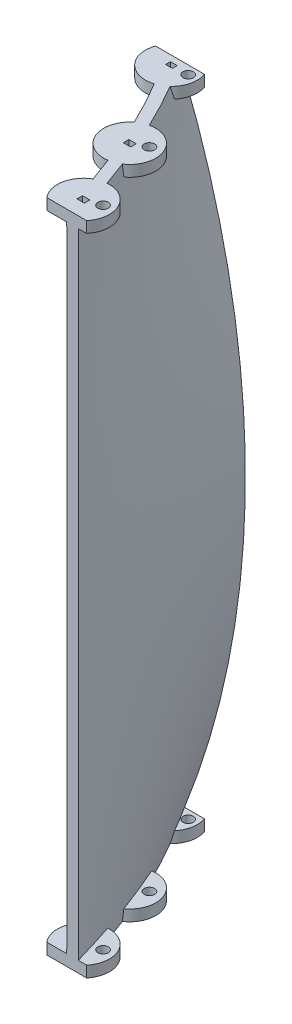
SolidWorks part; units mm, degrees
ref_plane "Plan de face" through (0, 0, 0) normal (0, 0, 1) x (1, 0, 0)
ref_plane "Plan de dessus" through (0, 0, 0) normal (0, 1, 0) x (1, 0, 0)
ref_plane "Plan de droite" through (0, 0, 0) normal (1, 0, 0) x (0, 0, -1)
ref_plane "Plan1" through (0, 0, 10) normal (0, 0, 1) x (1, 0, 0)
ref_plane "Plan2" through (0, 0, 60) normal (0, 0, 1) x (1, 0, 0)
sketch "Esquisse1" plane through (0, 0, 60) normal (0, 0, 1) x (1, 0, 0)
  line L1 (-235, -265) -> (235, -265)
  line L2 (-235, -265) -> (-235, 265)
  line L3 (-235, 265) -> (235, 265)
  line L4 (235, -265) -> (235, 265)
  line L5 (-235, -265) -> (235, 265) construction
  line L6 (-235, 265) -> (235, -265) construction
  point P0 (0, 0)
  dimension "D1" = 470
  dimension "D2" = 530
sketch "Esquisse2" plane through (0, 0, 10) normal (0, 0, 1) x (1, 0, 0)
  circle A0 centre (0, 0) radius 230
loft "Lissage1" add profiles "Esquisse2", "Esquisse1" connector at (-217.3645, 75.1842, 10) connector at (-235, 265, 60)
shell "Coque1" thickness 3 removed face at (0, 0, 60)
sketch "Esquisse3" plane through (0, 0, 13) normal (0, 0, 1) x (1, 0, 0)
  spline S4 degree 3 poles (-1744.7327, 376.1903) (-526.9338, -261.2431) (-3.804, -346.9049) (174.7035, -148.6101) (179.7346, -142.3812) (189.1199, -129.386) (193.4749, -122.6201) (198.4789, -113.8135) (199.4591, -112.0321) (201.3646, -108.4534) (202.2908, -106.6549) (204.9907, -101.232) (206.6856, -97.5804) (211.4617, -86.5187) (214.236, -79.0024) (218.9895, -63.6942) (220.9703, -55.9031) (222.9555, -45.9941) (223.3279, -44.0038) (224.0237, -40.0062) (224.3459, -38.0049) (225.2353, -32.0028) (225.7261, -28) (226.8998, -15.9875) (227.2865, -7.9737) (227.2836, 8.0646) (226.894, 16.0892) (225.9081, 26.1268) (225.6858, 28.1347) (225.1902, 32.1512) (224.9166, 34.1622) (224.021, 40.178) (223.3259, 44.156) (220.9479, 55.9928) (218.9722, 63.7545) (214.2305, 79.0156) (211.4628, 86.5145) (206.6954, 97.5584) (205.0032, 101.2055) (202.3067, 106.6237) (201.3815, 108.421) (199.4777, 111.9979) (198.4976, 113.78) (193.4909, 122.5945) (189.1338, 129.3656) (179.7439, 142.3695) (174.7107, 148.6017) (-4.1787, 347.3344) (-528.7451, 260.2995) (-1744.2878, -377.4815) knots -1.953743 -1.953743 -1.953743 -1.953743 0.0625 0.0625 0.125 0.125 0.1875 0.1875 0.203125 0.203125 0.21875 0.21875 0.25 0.25 0.3125 0.3125 0.375 0.375 0.390625 0.390625 0.40625 0.40625 0.4375 0.4375 0.5 0.5 0.5625 0.5625 0.578125 0.578125 0.59375 0.59375 0.625 0.625 0.6875 0.6875 0.75 0.75 0.78125 0.78125 0.796875 0.796875 0.8125 0.8125 0.875 0.875 0.9375 0.9375 2.957415 2.957415 2.957415 2.957415 only from (152.2162, -171.6485) to (152.2162, 171.6485)
  spline S5 degree 3 poles (-195.2618, -1771.3819) (316.1646, -491.0086) (344.6975, 32.7076) (130.3839, 188.7229) (124.6273, 192.5237) (112.7752, 199.5943) (106.68, 202.8645) (98.8449, 206.6138) (97.2671, 207.3467) (94.0897, 208.7785) (92.4898, 209.4774) (87.681, 211.5127) (84.4552, 212.7913) (74.7194, 216.3971) (68.1511, 218.4952) (54.8632, 222.0955) (48.1436, 223.5983) (34.5539, 226.0114) (27.684, 226.9224) (19.0006, 227.6836) (17.263, 227.8166) (13.7931, 228.0438) (12.0597, 228.1381) (6.8641, 228.3641) (3.4064, 228.4387) (-6.9486, 228.4367) (-13.828, 228.1355) (-27.5391, 226.9367) (-34.3709, 226.0386) (-44.5819, 224.2333) (-47.9794, 223.5547) (-53.0663, 222.4195) (-54.7604, 222.0216) (-58.1454, 221.1859) (-59.8336, 220.7489) (-68.2258, 218.4749) (-74.8099, 216.3655) (-87.7243, 211.5786) (-94.0544, 208.9004) (-106.4603, 202.9753) (-112.536, 199.7278) (-121.4549, 194.4207) (-124.3952, 192.5788) (-128.7561, 189.7046) (-130.2026, 188.7271) (-133.0695, 186.7413) (-134.4907, 185.7324) (-375.502, 10.4249) (-260.223, -622.6751) (244.4446, -1759.2058) knots -2.272579 -2.272579 -2.272579 -2.272579 0.0625 0.0625 0.125 0.125 0.1875 0.1875 0.203125 0.203125 0.21875 0.21875 0.25 0.25 0.3125 0.3125 0.375 0.375 0.4375 0.4375 0.453125 0.453125 0.46875 0.46875 0.5 0.5 0.5625 0.5625 0.625 0.625 0.65625 0.65625 0.671875 0.671875 0.6875 0.6875 0.75 0.75 0.8125 0.8125 0.875 0.875 0.90625 0.90625 0.921875 0.921875 0.9375 0.9375 3.594862 3.594862 3.594862 3.594862 only from (152.2162, 171.6485) to (-152.2162, 171.6485)
  spline S6 degree 3 poles (1744.7327, -376.1903) (526.9338, 261.2431) (3.804, 346.9049) (-174.7035, 148.6101) (-179.7346, 142.3812) (-189.1199, 129.386) (-193.4749, 122.6201) (-198.4789, 113.8135) (-199.4591, 112.0321) (-201.3646, 108.4534) (-202.2908, 106.6549) (-204.9907, 101.232) (-206.6856, 97.5804) (-211.4617, 86.5187) (-214.236, 79.0024) (-218.9895, 63.6942) (-220.9703, 55.9031) (-222.9555, 45.9941) (-223.3279, 44.0038) (-224.0237, 40.0062) (-224.3459, 38.0049) (-225.2353, 32.0028) (-225.7261, 28) (-226.8998, 15.9875) (-227.2865, 7.9737) (-227.2836, -8.0646) (-226.894, -16.0892) (-225.9081, -26.1268) (-225.6858, -28.1347) (-225.1902, -32.1512) (-224.9166, -34.1622) (-224.021, -40.178) (-223.3259, -44.156) (-220.9479, -55.9928) (-218.9722, -63.7545) (-214.2305, -79.0156) (-211.4628, -86.5145) (-206.6954, -97.5584) (-205.0032, -101.2055) (-202.3067, -106.6237) (-201.3815, -108.421) (-199.4777, -111.9979) (-198.4976, -113.78) (-193.4909, -122.5945) (-189.1338, -129.3656) (-179.7439, -142.3695) (-174.7107, -148.6017) (4.1787, -347.3344) (528.7451, -260.2995) (1744.2878, 377.4815) knots -1.953743 -1.953743 -1.953743 -1.953743 0.0625 0.0625 0.125 0.125 0.1875 0.1875 0.203125 0.203125 0.21875 0.21875 0.25 0.25 0.3125 0.3125 0.375 0.375 0.390625 0.390625 0.40625 0.40625 0.4375 0.4375 0.5 0.5 0.5625 0.5625 0.578125 0.578125 0.59375 0.59375 0.625 0.625 0.6875 0.6875 0.75 0.75 0.78125 0.78125 0.796875 0.796875 0.8125 0.8125 0.875 0.875 0.9375 0.9375 2.957415 2.957415 2.957415 2.957415 only from (-152.2162, 171.6485) to (-152.2162, -171.6485)
  spline S7 degree 3 poles (195.2618, 1771.3819) (-316.1646, 491.0086) (-344.6975, -32.7076) (-130.3839, -188.7229) (-124.6273, -192.5237) (-112.7752, -199.5943) (-106.68, -202.8645) (-98.8449, -206.6138) (-97.2671, -207.3467) (-94.0897, -208.7785) (-92.4898, -209.4774) (-87.681, -211.5127) (-84.4552, -212.7913) (-74.7194, -216.3971) (-68.1511, -218.4952) (-54.8632, -222.0955) (-48.1436, -223.5983) (-34.5539, -226.0114) (-27.684, -226.9224) (-19.0006, -227.6836) (-17.263, -227.8166) (-13.7931, -228.0438) (-12.0597, -228.1381) (-6.8641, -228.3641) (-3.4064, -228.4387) (6.9486, -228.4367) (13.828, -228.1355) (27.5391, -226.9367) (34.3709, -226.0386) (44.5819, -224.2333) (47.9794, -223.5547) (53.0663, -222.4195) (54.7604, -222.0216) (58.1454, -221.1859) (59.8336, -220.7489) (68.2258, -218.4749) (74.8099, -216.3655) (87.7243, -211.5786) (94.0544, -208.9004) (106.4603, -202.9753) (112.536, -199.7278) (121.4549, -194.4207) (124.3952, -192.5788) (128.7561, -189.7046) (130.2026, -188.7271) (133.0695, -186.7413) (134.4907, -185.7324) (375.502, -10.4249) (260.223, 622.6751) (-244.4446, 1759.2058) knots -2.272579 -2.272579 -2.272579 -2.272579 0.0625 0.0625 0.125 0.125 0.1875 0.1875 0.203125 0.203125 0.21875 0.21875 0.25 0.25 0.3125 0.3125 0.375 0.375 0.4375 0.4375 0.453125 0.453125 0.46875 0.46875 0.5 0.5 0.5625 0.5625 0.625 0.625 0.65625 0.65625 0.671875 0.671875 0.6875 0.6875 0.75 0.75 0.8125 0.8125 0.875 0.875 0.90625 0.90625 0.921875 0.921875 0.9375 0.9375 3.594862 3.594862 3.594862 3.594862 only from (-152.2162, -171.6485) to (152.2162, -171.6485)
  spline S8 degree 3 poles (152.2162, -171.6485) (158.2661, -166.2289) (163.9694, -160.534) (174.7035, -148.6101) (179.7346, -142.3812) (189.1199, -129.386) (193.4749, -122.6201) (198.4789, -113.8135) (199.4591, -112.0321) (201.3646, -108.4534) (202.2908, -106.6549) (204.9907, -101.232) (206.6856, -97.5804) (211.4617, -86.5187) (214.236, -79.0024) (218.9895, -63.6942) (220.9703, -55.9031) (222.9555, -45.9941) (223.3279, -44.0038) (224.0237, -40.0062) (224.3459, -38.0049) (225.2353, -32.0028) (225.7261, -28) (226.8998, -15.9875) (227.2865, -7.9737) (227.2836, 8.0646) (226.894, 16.0892) (225.9081, 26.1268) (225.6858, 28.1347) (225.1902, 32.1512) (224.9166, 34.1622) (224.021, 40.178) (223.3259, 44.156) (220.9479, 55.9928) (218.9722, 63.7545) (214.2305, 79.0156) (211.4628, 86.5145) (206.6954, 97.5584) (205.0032, 101.2055) (202.3067, 106.6237) (201.3815, 108.421) (199.4777, 111.9979) (198.4976, 113.78) (193.4909, 122.5945) (189.1338, 129.3656) (179.7439, 142.3695) (174.7107, 148.6017) (163.9726, 160.5309) (158.2675, 166.2277) (152.2162, 171.6485) knots 0 0 0 0 0.0625 0.0625 0.125 0.125 0.1875 0.1875 0.203125 0.203125 0.21875 0.21875 0.25 0.25 0.3125 0.3125 0.375 0.375 0.390625 0.390625 0.40625 0.40625 0.4375 0.4375 0.5 0.5 0.5625 0.5625 0.578125 0.578125 0.59375 0.59375 0.625 0.625 0.6875 0.6875 0.75 0.75 0.78125 0.78125 0.796875 0.796875 0.8125 0.8125 0.875 0.875 0.9375 0.9375 1 1 1 1
  spline S9 degree 3 poles (152.2162, 171.6485) (146.9741, 176.2555) (141.5573, 180.5889) (130.3839, 188.7229) (124.6273, 192.5237) (112.7752, 199.5943) (106.68, 202.8645) (98.8449, 206.6138) (97.2671, 207.3467) (94.0897, 208.7785) (92.4898, 209.4774) (87.681, 211.5127) (84.4552, 212.7913) (74.7194, 216.3971) (68.1511, 218.4952) (54.8632, 222.0955) (48.1436, 223.5983) (34.5539, 226.0114) (27.684, 226.9224) (19.0006, 227.6836) (17.263, 227.8166) (13.7931, 228.0438) (12.0597, 228.1381) (6.8641, 228.3641) (3.4064, 228.4387) (-6.9486, 228.4367) (-13.828, 228.1355) (-27.5391, 226.9367) (-34.3709, 226.0386) (-44.5819, 224.2333) (-47.9794, 223.5547) (-53.0663, 222.4195) (-54.7604, 222.0216) (-58.1454, 221.1859) (-59.8336, 220.7489) (-68.2258, 218.4749) (-74.8099, 216.3655) (-87.7243, 211.5786) (-94.0544, 208.9004) (-106.4603, 202.9753) (-112.536, 199.7278) (-121.4549, 194.4207) (-124.3952, 192.5788) (-128.7561, 189.7046) (-130.2026, 188.7271) (-133.0695, 186.7413) (-134.4907, 185.7324) (-141.5348, 180.6086) (-146.9739, 176.2557) (-152.2162, 171.6485) knots 0 0 0 0 0.0625 0.0625 0.125 0.125 0.1875 0.1875 0.203125 0.203125 0.21875 0.21875 0.25 0.25 0.3125 0.3125 0.375 0.375 0.4375 0.4375 0.453125 0.453125 0.46875 0.46875 0.5 0.5 0.5625 0.5625 0.625 0.625 0.65625 0.65625 0.671875 0.671875 0.6875 0.6875 0.75 0.75 0.8125 0.8125 0.875 0.875 0.90625 0.90625 0.921875 0.921875 0.9375 0.9375 1 1 1 1
  spline S10 degree 3 poles (-152.2162, 171.6485) (-158.2661, 166.2289) (-163.9694, 160.534) (-174.7035, 148.6101) (-179.7346, 142.3812) (-189.1199, 129.386) (-193.4749, 122.6201) (-198.4789, 113.8135) (-199.4591, 112.0321) (-201.3646, 108.4534) (-202.2908, 106.6549) (-204.9907, 101.232) (-206.6856, 97.5804) (-211.4617, 86.5187) (-214.236, 79.0024) (-218.9895, 63.6942) (-220.9703, 55.9031) (-222.9555, 45.9941) (-223.3279, 44.0038) (-224.0237, 40.0062) (-224.3459, 38.0049) (-225.2353, 32.0028) (-225.7261, 28) (-226.8998, 15.9875) (-227.2865, 7.9737) (-227.2836, -8.0646) (-226.894, -16.0892) (-225.9081, -26.1268) (-225.6858, -28.1347) (-225.1902, -32.1512) (-224.9166, -34.1622) (-224.021, -40.178) (-223.3259, -44.156) (-220.9479, -55.9928) (-218.9722, -63.7545) (-214.2305, -79.0156) (-211.4628, -86.5145) (-206.6954, -97.5584) (-205.0032, -101.2055) (-202.3067, -106.6237) (-201.3815, -108.421) (-199.4777, -111.9979) (-198.4976, -113.78) (-193.4909, -122.5945) (-189.1338, -129.3656) (-179.7439, -142.3695) (-174.7107, -148.6017) (-163.9726, -160.5309) (-158.2675, -166.2277) (-152.2162, -171.6485) knots 0 0 0 0 0.0625 0.0625 0.125 0.125 0.1875 0.1875 0.203125 0.203125 0.21875 0.21875 0.25 0.25 0.3125 0.3125 0.375 0.375 0.390625 0.390625 0.40625 0.40625 0.4375 0.4375 0.5 0.5 0.5625 0.5625 0.578125 0.578125 0.59375 0.59375 0.625 0.625 0.6875 0.6875 0.75 0.75 0.78125 0.78125 0.796875 0.796875 0.8125 0.8125 0.875 0.875 0.9375 0.9375 1 1 1 1
  spline S11 degree 3 poles (-152.2162, -171.6485) (-146.9741, -176.2555) (-141.5573, -180.5889) (-130.3839, -188.7229) (-124.6273, -192.5237) (-112.7752, -199.5943) (-106.68, -202.8645) (-98.8449, -206.6138) (-97.2671, -207.3467) (-94.0897, -208.7785) (-92.4898, -209.4774) (-87.681, -211.5127) (-84.4552, -212.7913) (-74.7194, -216.3971) (-68.1511, -218.4952) (-54.8632, -222.0955) (-48.1436, -223.5983) (-34.5539, -226.0114) (-27.684, -226.9224) (-19.0006, -227.6836) (-17.263, -227.8166) (-13.7931, -228.0438) (-12.0597, -228.1381) (-6.8641, -228.3641) (-3.4064, -228.4387) (6.9486, -228.4367) (13.828, -228.1355) (27.5391, -226.9367) (34.3709, -226.0386) (44.5819, -224.2333) (47.9794, -223.5547) (53.0663, -222.4195) (54.7604, -222.0216) (58.1454, -221.1859) (59.8336, -220.7489) (68.2258, -218.4749) (74.8099, -216.3655) (87.7243, -211.5786) (94.0544, -208.9004) (106.4603, -202.9753) (112.536, -199.7278) (121.4549, -194.4207) (124.3952, -192.5788) (128.7561, -189.7046) (130.2026, -188.7271) (133.0695, -186.7413) (134.4907, -185.7324) (141.5348, -180.6086) (146.9739, -176.2557) (152.2162, -171.6485) knots 0 0 0 0 0.0625 0.0625 0.125 0.125 0.1875 0.1875 0.203125 0.203125 0.21875 0.21875 0.25 0.25 0.3125 0.3125 0.375 0.375 0.4375 0.4375 0.453125 0.453125 0.46875 0.46875 0.5 0.5 0.5625 0.5625 0.625 0.625 0.65625 0.65625 0.671875 0.671875 0.6875 0.6875 0.75 0.75 0.8125 0.8125 0.875 0.875 0.90625 0.90625 0.921875 0.921875 0.9375 0.9375 1 1 1 1
  dimension "D1" = 0
extrude "Enlèv. mat.-Extru.1" cut sketch "Esquisse3" against normal blind 10
sketch "Esquisse4" plane through (0, 0, 0) normal (0, 1, 0) x (1, 0, 0)
  line L0 (-55, -10) -> (55, -10) construction
  line L1 (-235, -10) -> (235, -10)
  line L2 (-235, -10) -> (-235, -60)
  line L3 (-235, -60) -> (235, -60)
  line L4 (235, -10) -> (235, -60)
  line L5 (-55, -60) -> (55, -60) construction
  line L6 (0, -10) -> (0, -60)
  point P10 (0, -60)
  point P13 (0, -10)
extrude "Enlèv. mat.-Extru.2" cut sketch "Esquisse4" against normal through all both and the other way through all contours L6 L1 L2 L3 region at (-117.5, 0, 35)
sketch "Esquisse7" plane through (0, 0, 0) normal (0, 0, 1) x (1, 0, 0)
  line L0 (0, -88.3333) -> (235, -88.3333)
  line L1 (0, 265) -> (235, 265)
  line L2 (0, 265) -> (0, -265)
  line L3 (0, -265) -> (235, -265)
  line L4 (235, 265) -> (235, -265)
  line L5 (0, 88.3333) -> (235, 88.3333)
  dimension "D1" = 176.6667
  dimension "D2" = 176.6667
extrude "Enlèv. mat.-Extru.7" cut sketch "Esquisse7" against normal through all both and the other way through all contours L4 L0 L2 L3 | L2 L5 L4 L1 region at (117.5, -176.6667, 0) region at (117.5, 176.6667, 0)
sketch "Esquisse8" plane through (0, 88.3333, 0) normal (0, 1, 0) x (1, 0, 0)
  line L0 (235, -60) -> (225, -60) construction
  line L1 (225, -60) -> (225, -36.15) construction
  line L2 (231.8645, -60) -> (231.8645, -55.5) construction
  line L3 (226, -35.4) -> (224, -35.4)
  line L4 (226, -35.4) -> (226, -36.9)
  line L5 (226, -36.9) -> (224, -36.9)
  line L6 (224, -35.4) -> (224, -36.9)
  line L7 (226, -35.4) -> (224, -36.9) construction
  line L8 (226, -36.9) -> (224, -35.4) construction
  line L9 (212.361, -10) -> (212.361, -12.3) construction
  line L10 (230.8645, -56.25) -> (232.8645, -56.25)
  line L11 (230.8645, -56.25) -> (230.8645, -54.75)
  line L12 (230.8645, -54.75) -> (232.8645, -54.75)
  line L13 (232.8645, -56.25) -> (232.8645, -54.75)
  line L14 (230.8645, -56.25) -> (232.8645, -54.75) construction
  line L15 (230.8645, -54.75) -> (232.8645, -56.25) construction
  line L16 (-13.4344, -10) -> (13.4344, -10) construction
  line L17 (218.9966, -10) -> (205.7902, -10)
  line L18 (211.461, -11.65) -> (213.261, -11.65)
  line L19 (211.461, -11.65) -> (211.461, -12.95)
  line L20 (211.461, -12.95) -> (213.261, -12.95)
  line L21 (213.261, -11.65) -> (213.261, -12.95)
  line L22 (211.461, -11.65) -> (213.261, -12.95) construction
  line L23 (211.461, -12.95) -> (213.261, -11.65) construction
  line L24 (226.5026, -60) -> (237.2264, -60)
  line L25 (206.3165, -16.3286) -> (218.0813, -8.7398) construction
  line L26 (214.4595, -19.0115) -> (207.1523, -7.6833) construction
  line L27 (214.4595, -19.0115) -> (207.1523, -7.6833) construction
  line L28 (218.4002, -38.9456) -> (231.2593, -33.41) construction
  line L29 (226.0432, -43.0718) -> (220.6892, -30.6348) construction
  line L30 (225.4311, -57.665) -> (238.7303, -53.2912) construction
  line L31 (232.6782, -62.4526) -> (228.3926, -49.4217) construction
  line L32 (228.3926, -49.4217) -> (232.6782, -62.4526) construction
  line L33 (225, -36.15) -> (227.9376, -42.5038) construction
  line L34 (231.8645, -55.5) -> (229.6479, -48.8602) construction
  line L35 (234.0303, -56.8542) -> (232.7816, -52.9816) construction
  line L36 (215.675, -15.0284) -> (215.6661, -15.014) construction
  line L37 (215.6661, -15.014) -> (213.938, -12.3234) construction
  line L38 (212.361, -12.3) -> (216.891, -12.3) construction
  line L39 (225, -36.15) -> (228.5, -36.15) construction
  line L40 (228.5, -36.15) -> (228.5, -34.35) construction
  line L41 (231.8645, -55.5) -> (235.8645, -55.5) construction
  line L42 (235.8645, -55.5) -> (235.8645, -54.2) construction
  line L43 (210.59, -12.2458) -> (211.461, -12.2458) construction
  line L44 (210.59, -10) -> (210.59, -13) construction
  arc A0 (205.7902, -10) -> (218.9966, -10) centre (212.3934, -12.3234) ccw
  circle A1 centre (225, -36.15) radius 7
  arc A2 (237.2264, -60) -> (226.5026, -60) centre (231.8645, -55.5) ccw
  arc A3 (226.5026, -60) -> (237.2264, -60) centre (231.8645, -55.5) ccw construction
  arc A4 (218.9966, -10) -> (205.7902, -10) centre (212.3934, -12.3234) ccw construction
  circle A8 centre (228.5, -34.35) radius 1.4
  circle A9 centre (235.8645, -54.2) radius 1.4
  circle A10 centre (216.891, -12.3) radius 1.4
  spline S0 degree 3 poles (210.59, -13) (213.0403, -16.5566) (215.2722, -20.2435) (218.3567, -25.9307) (219.3418, -27.8544) (221.2286, -31.7389) (222.1304, -33.6994) (224.726, -39.6291) (226.3118, -43.6495) (229.2497, -51.7695) (230.6021, -55.8693) (231.8645, -60) knots 0 0 0 0 0.25 0.25 0.375 0.375 0.5 0.5 0.75 0.75 1 1 1 1 construction
  spline S1 degree 3 poles (212.361, -10) (214.9908, -13.7747) (217.3789, -17.6908) (220.6719, -23.734) (221.7217, -25.7777) (223.733, -29.9109) (225.6529, -34.0835) (227.4125, -38.3253) (229.1017, -42.5976) (229.9111, -44.7493) (232.2428, -51.2344) (233.6703, -55.6006) (235, -60) knots 0 0 0 0 0.25 0.25 0.375 0.375 0.5 0.625 0.625 0.75 0.75 1 1 1 1 construction
  point P38 (220.6892, -30.6348)
  point P39 (226.0432, -43.0718)
  point P40 (228.3926, -49.4217)
  point P41 (214.4595, -19.0115)
  point P42 (162.6307, -11.65)
  dimension "D11" = 2.8
  dimension "D12" = 3.5
  dimension "D14" = 4
  dimension "D16" = 2.8
  dimension "D5" = 1.3
  dimension "D17" = 2.8
  dimension "D1" = 10
  dimension "D2" = 23.85
  dimension "D3" = 2
  dimension "D4" = 1.5
  dimension "D6" = 2
  dimension "D7" = 1.5
  dimension "D8" = 2.3
  dimension "D9" = 1.8
  dimension "D10" = 1.3
  dimension "D13" = 1.8
  dimension "D15" = 4.53
extrude "Enlèv. mat.-Extru.8" cut sketch "Esquisse8" against normal blind 2 contours L10 L13 L12 L11 | L21 L18 L19 L20 | L6 L5 L4 L3 region at (231.8645, 88.3333, 55.5) region at (212.361, 88.3333, 12.3)
sketch "Esquisse9" plane through (0, -88.3333, 0) normal (0, -1, 0) x (1, 0, 0)
  line L0 (235, 60) -> (225, 60) construction
  line L1 (13.4344, 60) -> (-13.4344, 60) construction
  line L2 (225, 60) -> (225, 36.15) construction
  line L3 (231.8645, 60) -> (231.8645, 55.5) construction
  line L4 (224, 35.4) -> (226, 35.4)
  line L5 (224, 35.4) -> (224, 36.9)
  line L6 (224, 36.9) -> (226, 36.9)
  line L7 (226, 35.4) -> (226, 36.9)
  line L8 (224, 35.4) -> (226, 36.9) construction
  line L9 (224, 36.9) -> (226, 35.4) construction
  line L10 (212.361, 10) -> (212.361, 12.3) construction
  line L11 (230.8645, 54.75) -> (232.8645, 54.75)
  line L12 (230.8645, 54.75) -> (230.8645, 56.25)
  line L13 (230.8645, 56.25) -> (232.8645, 56.25)
  line L14 (232.8645, 54.75) -> (232.8645, 56.25)
  line L15 (230.8645, 54.75) -> (232.8645, 56.25) construction
  line L16 (230.8645, 56.25) -> (232.8645, 54.75) construction
  line L17 (226.5026, 60) -> (237.2264, 60)
  line L18 (213.261, 11.65) -> (211.461, 11.65)
  line L19 (213.261, 11.65) -> (213.261, 12.95)
  line L20 (213.261, 12.95) -> (211.461, 12.95)
  line L21 (211.461, 11.65) -> (211.461, 12.95)
  line L22 (213.261, 11.65) -> (211.461, 12.95) construction
  line L23 (213.261, 12.95) -> (211.461, 11.65) construction
  line L24 (205.7497, 10) -> (218.9724, 10)
  line L25 (212.361, 10) -> (230, 10) construction
  line L26 (235.8645, 55.5) -> (235.8645, 54.2) construction
  line L27 (210.5899, 12.0521) -> (211.461, 12.0521) construction
  line L28 (231.8645, 55.5) -> (235.8645, 55.5) construction
  line L29 (210.59, 10) -> (210.5899, 12.9999) construction
  line L30 (228.5, 36.15) -> (228.5, 34.35) construction
  line L31 (212.361, 12.3) -> (216.891, 12.3) construction
  line L32 (225, 36.15) -> (228.5, 36.15) construction
  arc A0 (226.5026, 60) -> (237.2264, 60) centre (231.8645, 55.5) ccw
  circle A1 centre (225, 36.15) radius 7
  arc A2 (218.9724, 10) -> (205.7497, 10) centre (212.361, 12.3) ccw
  arc A3 (237.2264, 60) -> (226.5026, 60) centre (231.8645, 55.5) ccw construction
  arc A4 (205.7497, 10) -> (218.9724, 10) centre (212.361, 12.3) ccw construction
  circle A5 centre (235.8645, 54.2) radius 1.4
  circle A6 centre (228.5, 34.35) radius 1.4
  circle A7 centre (216.891, 12.3) radius 1.4
  dimension "D11" = 1.3
  dimension "D12" = 2.8
  dimension "D16" = 2.8
  dimension "D19" = 2.8
  dimension "D1" = 10
  dimension "D2" = 23.85
  dimension "D3" = 2
  dimension "D4" = 1.5
  dimension "D5" = 4.5
  dimension "D6" = 2
  dimension "D7" = 1.5
  dimension "D8" = 2.3
  dimension "D9" = 1.8
  dimension "D10" = 1.3
  dimension "D13" = 4
  dimension "D14" = 4.53
  dimension "D15" = 1.8
  dimension "D17" = 3.5
extrude "Enlèv. mat.-Extru.9" cut sketch "Esquisse9" against normal blind 2 contours L19 L18 L21 L20 | L12 L11 L14 L13 | L5 L4 L7 L6
extrude "Boss.-Extru.2" add sketch "Esquisse8<3>" against normal blind 3
sketch "Esquisse8<3>" plane through (0, 88.3333, 0) normal (0, 1, 0) x (1, 0, 0) same geometry as "Esquisse8"
extrude "Boss.-Extru.3" add sketch "Esquisse9<3>" against normal blind 3
sketch "Esquisse9<3>" plane through (0, -88.3333, 0) normal (0, -1, 0) x (1, 0, 0) same geometry as "Esquisse9"
